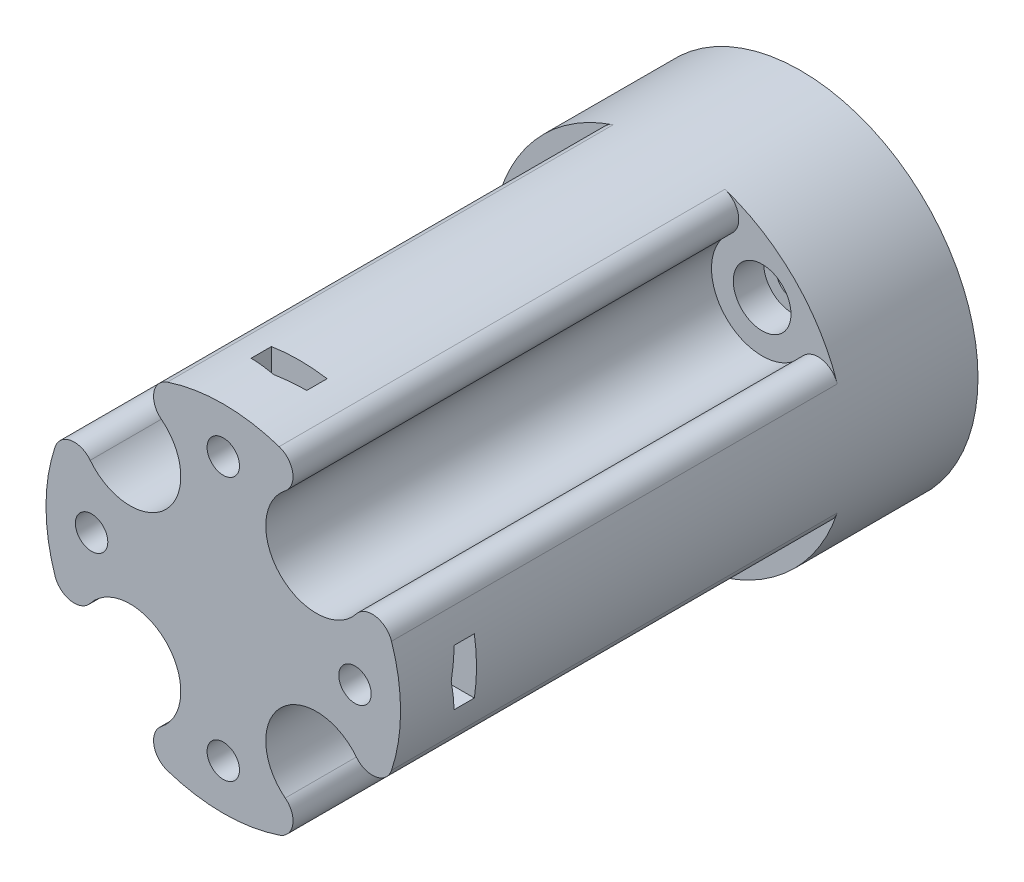
SolidWorks part; units mm, degrees
ref_plane "Front Plane" through (0, 0, 0) normal (1, 0, 0) x (0, 1, 0)
ref_plane "Top Plane" through (0, 0, 0) normal (0, 0, 1) x (0, 1, 0)
ref_plane "Right Plane" through (0, 0, 0) normal (0, 1, 0) x (-1, 0, 0)
sketch "Sketch1" plane through (0, 0, 0) normal (0, 0, 1) x (0, 1, 0)
  line L0 (0, 0) -> (9.1924, 9.1924) construction
  circle A0 centre (0, 0) radius 17.5
  circle A1 centre (0, 0) radius 13 construction
  circle A2 centre (9.1924, 9.1924) radius 1.6
  circle A3 centre (9.1924, 9.1924) radius 2.85
  circle A4 centre (9.1924, -9.1924) radius 2.85
  circle A5 centre (9.1924, -9.1924) radius 1.6
  circle A6 centre (-9.1924, -9.1924) radius 2.85
  circle A7 centre (-9.1924, -9.1924) radius 1.6
  circle A8 centre (-9.1924, 9.1924) radius 2.85
  circle A9 centre (-9.1924, 9.1924) radius 1.6
  point P19 (0, 0)
  dimension "D1" = 35
  dimension "D2" = 26
  dimension "D3" = 3.2
  dimension "D4" = 5.7
  dimension "D5" = 4
extrude "Boss-Extrude1" add sketch "Sketch1" along normal blind 57 contours A0 A8 A6 A4 A3 region at (0, 0, 0)
extrude "Boss-Extrude2" add sketch "Sketch1<3>" along normal blind 10 contours A6 A7 | A8 A9 | A4 A5 | A3 A2 region at (-9.1924, 6.423, 0) region at (9.1924, 6.423, 0) region at (9.1924, -11.9618, 0) region at (-9.1924, -11.9618, 0)
sketch "Sketch1<3>" plane through (0, 0, 0) normal (0, 0, 1) x (0, 1, 0) same geometry as "Sketch1"
sketch "Sketch2" plane through (0, 0, 57) normal (0, 0, 1) x (1, 0, 0)
  circle A0 centre (-9.1924, 9.1924) radius 5
  circle A1 centre (9.1924, 9.1924) radius 5
  circle A2 centre (9.1924, -9.1924) radius 5
  circle A3 centre (-9.1924, -9.1924) radius 5
  dimension "D1" = 10
  dimension "D2" = 2
  dimension "D3" = 2
extrude "Cut-Extrude1" cut sketch "Sketch2" against normal blind 44
fillet "Fillet1" radius 2 8 edges at (14.0286, 10.4618, 35) (-14.0286, 10.4618, 35) (-10.4618, 14.0286, 35) (10.4618, 14.0286, 35) (14.0286, -10.4618, 35) (10.4618, -14.0286, 35) (-10.4618, -14.0286, 35) (-14.0286, -10.4618, 35)
sketch "Sketch3" plane through (0, 0, 57) normal (0, 0, 1) x (1, 0, 0)
  line L0 (-2.75, 15.75) -> (-2.75, 17.2826)
  line L2 (-2.75, 15.75) -> (-2.75, 10.25)
  line L3 (-2.75, 10.25) -> (2.75, 10.25)
  line L4 (2.75, 15.75) -> (2.75, 10.25)
  line L5 (-2.75, 15.75) -> (2.75, 10.25) construction
  line L6 (-2.75, 10.25) -> (2.75, 15.75) construction
  line L7 (2.75, 15.75) -> (2.75, 17.2826)
  line L8 (15.75, -2.75) -> (10.25, -2.75)
  line L9 (10.25, 2.75) -> (10.25, -2.75)
  line L10 (15.75, 2.75) -> (10.25, 2.75)
  line L11 (15.75, 2.75) -> (17.2826, 2.75)
  line L12 (15.75, -2.75) -> (17.2826, -2.75)
  line L13 (-2.75, -15.75) -> (-2.75, -10.25)
  line L14 (2.75, -10.25) -> (-2.75, -10.25)
  line L15 (2.75, -15.75) -> (2.75, -10.25)
  line L16 (2.75, -15.75) -> (2.75, -17.2826)
  line L17 (-2.75, -15.75) -> (-2.75, -17.2826)
  line L18 (-15.75, 2.75) -> (-10.25, 2.75)
  line L19 (-10.25, -2.75) -> (-10.25, 2.75)
  line L20 (-15.75, -2.75) -> (-10.25, -2.75)
  line L21 (-15.75, -2.75) -> (-17.2826, -2.75)
  line L22 (-15.75, 2.75) -> (-17.2826, 2.75)
  circle A0 centre (0, 0) radius 13 construction
  circle A2 centre (0, 13) radius 1.6
  arc A3 (5.5152, 16.6082) -> (-5.5152, 16.6082) centre (0, 0) ccw construction
  arc A4 (-2.75, 17.2826) -> (2.75, 17.2826) centre (0, 0) cw
  arc A5 (17.2826, 2.75) -> (17.2826, -2.75) centre (0, 0) cw
  circle A6 centre (13, 0) radius 1.6
  arc A7 (2.75, -17.2826) -> (-2.75, -17.2826) centre (0, 0) cw
  circle A8 centre (0, -13) radius 1.6
  arc A9 (-17.2826, -2.75) -> (-17.2826, 2.75) centre (0, 0) cw
  circle A10 centre (-13, 0) radius 1.6
  point P41 (0, 0)
  dimension "D1" = 26
  dimension "D2" = 3.2
  dimension "D3" = 5.5
  dimension "D4" = 5.5
  dimension "D5" = 4
extrude "Cut-Extrude2" cut sketch "Sketch3" against normal blind 2.5 from offset 5 offset against normal yes
extrude "Cut-Extrude3" cut sketch "Sketch3<2>" against normal blind 10 contours A10 | A2 | A6 | A8 region at (0, 13, 57) region at (13, 0, 57) region at (0, -13, 57) region at (-13, 0, 57)
sketch "Sketch3<2>" plane through (0, 0, 57) normal (0, 0, 1) x (1, 0, 0) same geometry as "Sketch3"
chamfer "Chamfer1" distance 2.75 distance2 0.5 8 edges at (-13.7663, -2.75, 52) (-2.75, 13.7663, 52) (2.75, 13.7663, 52) (13.7663, 2.75, 52) (13.7663, -2.75, 52) (2.75, -13.7663, 52) (-2.75, -13.7663, 52) (-13.7663, 2.75, 52) first distance on face at (-14.6, 0, 52) first distance on face at (-1.6, 13, 52) first distance on face at (11.4, 0, 52) first distance on face at (-1.6, -13, 52)
